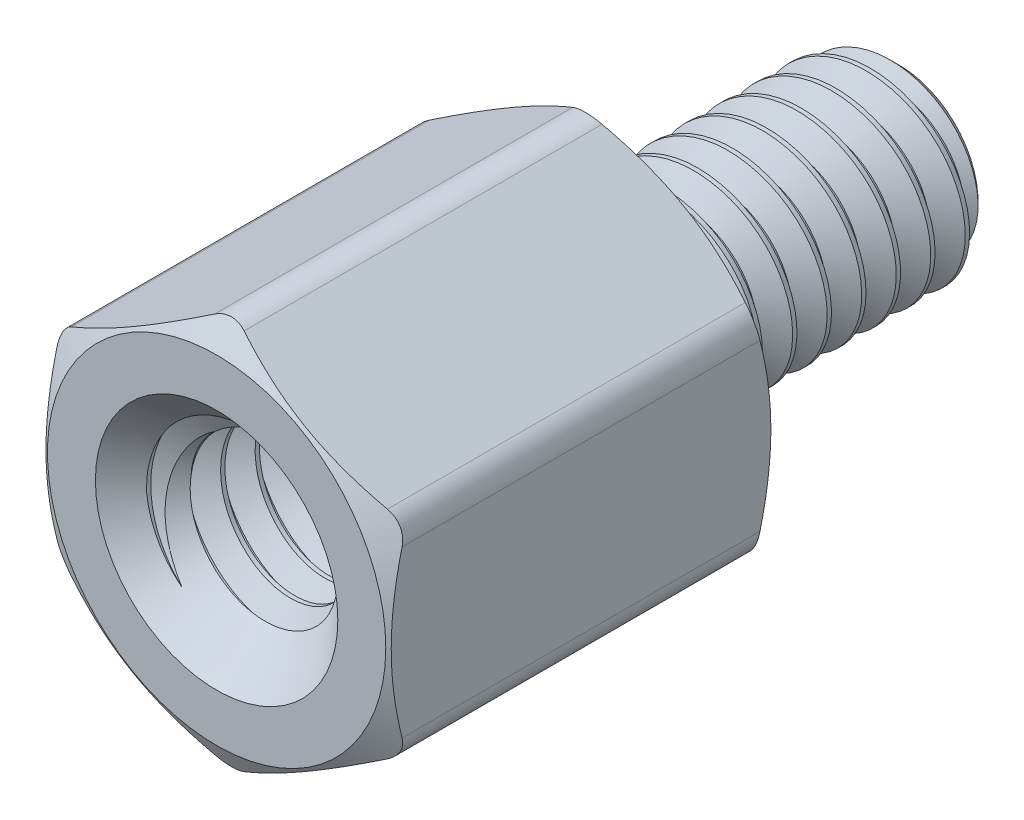
SolidWorks part; units mm, degrees
ref_plane "Front Plane" through (0, 0, 0) normal (0, 0, 1) x (1, 0, 0)
ref_plane "Top Plane" through (0, 0, 0) normal (0, 1, 0) x (1, 0, 0)
ref_plane "Right Plane" through (0, 0, 0) normal (1, 0, 0) x (0, 0, -1)
sketch "Sketch1" plane through (0, 0, 0) normal (0, 0, 1) x (1, 0, 0)
  line L1 (2.25, 1.299) -> (0, 2.5981)
  line L2 (0, 2.5981) -> (-2.25, 1.299)
  line L3 (-2.25, 1.299) -> (-2.25, -1.299)
  line L4 (-2.25, -1.299) -> (0, -2.5981)
  line L5 (0, -2.5981) -> (2.25, -1.299)
  line L6 (2.25, -1.299) -> (2.25, 1.299)
  circle A0 centre (0, 0) radius 2.25 construction
  point P10 (0, -2.25)
  dimension "Hex Size" = 4.5
sketch "Sketch2" plane through (0, 0, 0) normal (1, 0, 0) x (0, 0, -1)
  line L0 (3.9, 0) -> (-5, 0) construction
  line L2 (0, 1.25) -> (0, -1.25) construction
  line L3 (-3.1, 1.25) -> (-3.1, -1.25) construction
  line L4 (-5.4219, 1.2987) -> (-5.1969, 0.909) construction
  line L5 (-5.1969, 0.909) -> (-4.9719, 1.2987) construction
  line L6 (-4.9719, 1.2987) -> (-5.4219, 1.2987) construction
  line L7 (-5.3938, 1.25) -> (-5, 1.25) construction
  line L8 (-5.225, 0.9577) -> (-5.1688, 0.9577) construction
  line L9 (-5.1969, 0.9577) -> (-5.1969, 0.909) construction
  line L10 (-5.1969, 1.25) -> (-5.1969, 1.2987) construction
  line L11 (3.8719, 1.2987) -> (4.3219, 1.2987) construction
  line L12 (4.3219, 1.2987) -> (4.0969, 0.909) construction
  line L13 (4.0969, 0.909) -> (3.8719, 1.2987) construction
  line L14 (3.9, 1.25) -> (4.2938, 1.25) construction
  line L15 (4.0687, 0.9577) -> (4.125, 0.9577) construction
  line L16 (4.0969, 0.9577) -> (4.0969, 0.909) construction
  line L17 (4.0969, 1.25) -> (4.0969, 1.2987) construction
  line L18 (0, 2.5981) -> (-5, 2.5981) construction
  point P6 (0, 0)
  point P9 (-3.1, 0)
  dimension "Length" = 5
sketch "Sketch3" plane through (0, 0, 0) normal (1, 0, 0) x (0, 0, -1)
  line L0 (-3.1, 0) -> (3.9, 0)
  line L1 (-3.1, 1.25) -> (-3.1, -1.25) construction
  line L2 (3.9, 0) -> (3.9, 1.025)
  line L3 (3.9, 1.025) -> (3.675, 1.25)
  line L4 (3.675, 1.25) -> (0.6367, 1.25)
  line L5 (0.6367, 1.25) -> (0.468, 0.9577)
  line L6 (-3.1, 0) -> (-3.1, 1.025)
  line L7 (-3.1, 1.025) -> (-3.325, 1.25)
  line L8 (-3.325, 1.25) -> (-4.775, 1.25)
  line L9 (-4.775, 1.25) -> (-5, 1.475)
  line L10 (3.675, 0) -> (3.675, -1.25) construction
  line L11 (-5, 1.475) -> (-5, 2.25)
  line L12 (-5, 2.25) -> (0, 2.25)
  line L14 (0.468, 0.9577) -> (0.225, 0.9577)
  line L15 (0, 1.1827) -> (0, 2.25)
  arc A0 (0, 1.1827) -> (0.225, 0.9577) centre (0.225, 1.1827) ccw
  point P5 (-5, -2.25)
  point P8 (-3.875, -1.25)
  point P9 (2.775, -1.25)
  point P27 (0, 0.9577)
  dimension "D4" = 0.225
  dimension "D2" = 0.225
  dimension "D1" = 45
  dimension "D6" = 1.125
  dimension "D7" = 60
  dimension "D3" = 1.125
  dimension "D5" = 0.468
revolve "Revolve1" add sketch "Sketch3" angle 360 about L0 region at (0, 1.0326, 0.6702)
sketch "Sketch4" plane through (0, 0, 5) normal (0, 0, 1) x (1, 0, 0)
  line L0 (0, 2.25) -> (0, 1.25) construction
  line L1 (-2.25, 1.299) -> (-2.25, -1.299)
  line L2 (-2.25, -1.299) -> (0, -2.5981)
  line L3 (0, -2.5981) -> (2.25, -1.299)
  line L4 (2.25, -1.299) -> (2.25, 1.299)
  line L5 (2.25, 1.299) -> (0, 2.5981)
  line L6 (0, 2.5981) -> (-2.25, 1.299)
  circle A0 centre (0, 0) radius 2.25 construction
  circle A1 centre (0, 0) radius 1.75
  circle A2 centre (0, 0) radius 2.25 construction
  point P16 (0, 1.75)
extrude "Boss-Extrude1" add sketch "Sketch4" against normal up to surface (5 mm away) up to face at (0, 2.25, 0)
sketch "Sketch5" plane through (0, 0, 5) normal (0, 0, 1) x (1, 0, 0)
  line L0 (-0.717, 1.0239) -> (0.717, -1.0239) construction
  line L1 (0, 1.25) -> (0, -1.25) construction
  line L3 (0, -3.7237) -> (0, 3.7237) construction
  circle A0 centre (0, 0) radius 2.205
  point P11 (0.717, -1.0239)
  dimension "D1" = 4.41
  dimension "D2" = 35
extrude "Cut-Extrude1" cut sketch "Sketch5" against normal through all draft 60 flip side to cut
sketch "Sketch6" plane through (0, 0, 0) normal (0, 0, -1) x (-1, 0, 0)
  circle A0 centre (0, 0) radius 2.205
  circle A1 centre (0, 0) radius 2.205 construction
extrude "Cut-Extrude2" cut sketch "Sketch6" against normal through all draft 60 flip side to cut
fillet "Fillet1" radius 0.3825 6 edges at (0, 2.5981, 2.5) (-2.25, -1.299, 2.5) (0, -2.5981, 2.5) (2.25, -1.299, 2.5) (2.25, 1.299, 2.5) (-2.25, 1.299, 2.5)
sketch "Drawing1" plane through (0, 0, 0) normal (1, 0, 0) x (0, 0, -1)
  line L0 (-5, 1.25) -> (-3.1, 1.25) construction
  line L1 (-3.1, 1.25) -> (-3.1, -1.25) construction
  line L2 (-3.1, -1.25) -> (-5, -1.25) construction
sketch "Sketch7" plane through (0, 0, 0) normal (-1, 0, 0) x (0, 0, 1)
  line L0 (-4.0687, 0.9577) -> (-4.125, 0.9577)
  line L1 (-4.125, 0.9577) -> (-4.3078, 1.2744)
  line L2 (-4.3219, 1.2987) -> (-4.0969, 0.909) construction
  line L3 (-4.3078, 1.2744) -> (-3.8859, 1.2744)
  line L4 (-4.0969, 0.909) -> (-3.8719, 1.2987) construction
  line L5 (-3.8859, 1.2744) -> (-4.0687, 0.9577)
  line L6 (-4.0969, 1.25) -> (-4.0969, 1.2987) construction
  point P12 (-4.0969, 1.2744)
sketch "Sketch8" plane through (0, 0, -3.9) normal (0, 0, -1) x (-1, 0, 0)
  circle A0 centre (0, 0) radius 1.25
curve "Helix/Spiral1" pitch 0.45 height 3.783 radius 1.25 centre (0, 0, -3.9) axis (0, 0, 1) start towards (0, 1, 0)
sweep "Cut-Sweep1" cut profiles "Sketch7" path "Helix/Spiral1" align with end faces yes
sketch "Sketch9" plane through (0, 0, 3.1) normal (0, 0, 1) x (1, 0, 0)
  circle A0 centre (0, 0) radius 1.475
extrude "Boss-Extrude2" add sketch "Sketch9" along normal up to surface (1.9 mm away) up to face at (0, 1.475, 5)
sketch "Sketch10" plane through (0, 0, 0) normal (1, 0, 0) x (0, 0, -1)
  line L0 (3.9, 0) -> (-5, 0) construction
  line L1 (-3.1, 1.25) -> (-5, 1.25)
  line L2 (-3.1, 1.25) -> (-3.1, 0)
  line L3 (-3.1, 0) -> (-5, 0)
  line L4 (-5, 1.25) -> (-5, 0)
revolve "Revolve2" add sketch "Sketch10" angle 360 about L0
sketch "Sketch11" plane through (0, 0, 5) normal (0, 0, 1) x (1, 0, 0)
  circle A0 centre (0, 0) radius 1.25
  circle A1 centre (0, 0) radius 1.25 construction
sketch "Sketch12" plane through (0, 0, 0) normal (1, 0, 0) x (0, 0, -1)
  line L0 (-5.225, 0.9577) -> (-5.1688, 0.9577)
  line L1 (-5.1688, 0.9577) -> (-4.9859, 1.2744)
  line L2 (-5.1969, 0.909) -> (-4.9719, 1.2987) construction
  line L3 (-4.9859, 1.2744) -> (-5.4078, 1.2744)
  line L4 (-5.4219, 1.2987) -> (-5.1969, 0.909) construction
  line L5 (-5.4078, 1.2744) -> (-5.225, 0.9577)
  line L6 (-5.1969, 1.25) -> (-5.1969, 1.2987) construction
  point P12 (-5.1969, 1.2744)
curve "Helix/Spiral2" pitch 0.45 height 2.35 radius 1.25 centre (0, 0, 5) axis (0, 0, -1) start towards (0, 1, 0)
sweep "Cut-Sweep2" cut profiles "Sketch12" path "Helix/Spiral2" align with end faces yes
combine bodies "Combine1" operation type subtract main body 113 bodies to subtract 114
sketch "Sketch13" plane through (0, 0, 5) normal (0, 0, 1) x (1, 0, 0)
  circle A0 centre (0, 0) radius 1.58
  dimension "D1" = 3.16
extrude "Cut-Extrude3" cut sketch "Sketch13" against normal through all draft 45
equation "\"Thread Pitch (B)/8@Sketch2\" = \"Thread Pitch (B)@Sketch2\" / 8"
equation "\"Thread Pitch (A)/8@Sketch2\" = \"Thread Pitch (A)@Sketch2\" / 8"
equation "\"D1@Sketch5\"=\"Hex Size@Sketch1\" * .98"
equation "\"D1@Fillet1\"=\"Hex Size@Sketch1\" * .085"
equation "\"D2@Sketch3\"=\"Thread Pitch (A)@Sketch2\" * .5"
equation "\"D4@Sketch3\" = \"D2@Sketch3\""
equation "\"D6@Sketch3\" = \"Thread Pitch (A)@Sketch2\" * 2.5"
equation "\"D3@Helix/Spiral1\" = \"Thread Length (A)@Sketch2\" - \"D5@Sketch3\" * .25"
equation "\"D4@Helix/Spiral1\" = \"Thread Pitch (A)@Sketch2\""
equation "\"D3@Sketch3\" = \"Thread Pitch (B)@Sketch2\" * 2.5"
equation "\"D5@Sketch3\" = \"Thread Length (A)@Sketch2\" * .12"
equation "\"D3@Helix/Spiral2\" = \"Minimum Thread Length (B)@Sketch2\" + \"Thread Pitch (B)@Sketch2\""
equation "\"D4@Helix/Spiral2\" = \"Thread Pitch (B)@Sketch2\""
equation "\"D1@Sketch13\"=(\"Hex Size@Sketch1\"-\"Thread Size (A)@Sketch2\")*.33+\"Thread Size (A)@Sketch2\""
